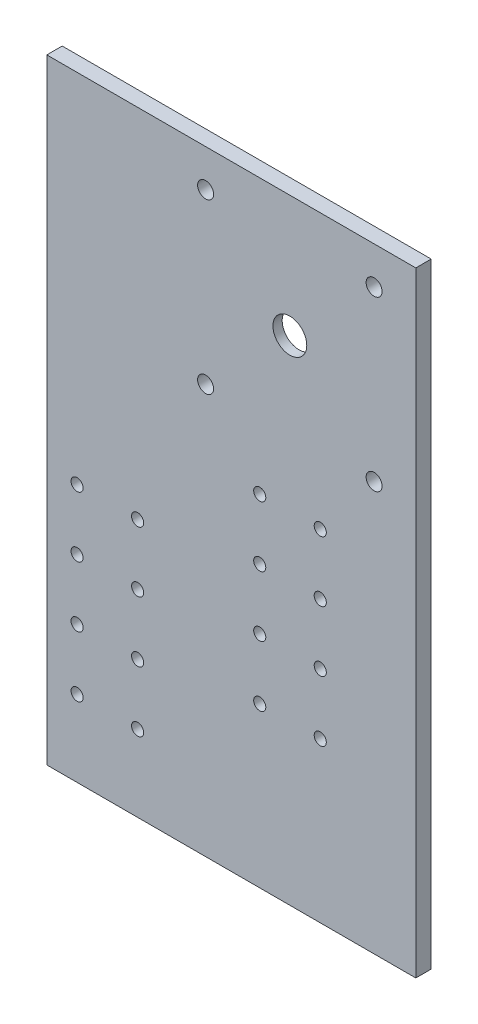
SolidWorks part; units mm, degrees
material "6061 Alloy"
ref_plane "Front Plane" through (0, 0, 0) normal (0, 0, 1) x (1, 0, 0)
ref_plane "Top Plane" through (0, 0, 0) normal (0, 1, 0) x (1, 0, 0)
ref_plane "Right Plane" through (0, 0, 0) normal (1, 0, 0) x (0, 0, -1)
sketch "Sketch1" plane through (0, 0, 0) normal (0, 0, 1) x (1, 0, 0)
  line L1 (-76.2, 127) -> (76.2, 127)
  line L2 (-76.2, 127) -> (-76.2, -127)
  line L3 (-76.2, -127) -> (76.2, -127)
  line L4 (76.2, 127) -> (76.2, -127)
  line L5 (-76.2, 127) -> (76.2, -127) construction
  line L6 (-76.2, -127) -> (76.2, 127) construction
  point P0 (0, 0)
  dimension "D1" = 254
  dimension "D2" = 152.4
extrude "Boss-Extrude1" add sketch "Sketch1" along normal blind 6.35
sketch "Sketch2" plane through (0, 0, 6.35) normal (0, 0, 1) x (1, 0, 0)
  circle A0 centre (58.979, 111.5609) radius 3.302 construction
  circle A1 centre (58.979, 111.5609) radius 3.302
  circle A2 centre (-10.617, 111.5609) radius 3.302 construction
  circle A3 centre (-10.617, 111.5609) radius 3.302
  circle A4 centre (58.98, 41.9649) radius 3.302 construction
  circle A5 centre (58.98, 41.9649) radius 3.302
  circle A6 centre (-10.618, 41.9639) radius 3.302 construction
  circle A7 centre (-10.618, 41.9639) radius 3.302
extrude "Cut-Extrude1" cut sketch "Sketch2" against normal up to next
sketch "Sketch3" plane through (0, 0, 0) normal (0, 0, -1) x (-1, 0, 0)
  circle A0 centre (63.7, -20.45) radius 2.5 construction
  circle A1 centre (63.7, -20.45) radius 2.5
  circle A2 centre (38.7, -20.45) radius 2.5 construction
  circle A3 centre (38.7, -45.45) radius 2.5 construction
  circle A4 centre (63.7, -45.45) radius 2.5 construction
  circle A5 centre (63.7, -70.45) radius 2.5 construction
  circle A6 centre (38.7, -70.45) radius 2.5 construction
  circle A7 centre (38.7, -95.45) radius 2.5 construction
  circle A8 centre (63.7, -95.45) radius 2.5 construction
  circle A9 centre (38.7, -20.45) radius 2.5
  circle A10 centre (38.7, -45.45) radius 2.5
  circle A11 centre (63.7, -45.45) radius 2.5
  circle A12 centre (63.7, -70.45) radius 2.5
  circle A13 centre (38.7, -70.45) radius 2.5
  circle A14 centre (38.7, -95.45) radius 2.5
  circle A15 centre (63.7, -95.45) radius 2.5
  circle A16 centre (-11.738, -61.16) radius 2.5 construction
  circle A17 centre (-11.738, -36.16) radius 2.5 construction
  circle A18 centre (-36.738, -61.16) radius 2.5 construction
  circle A19 centre (-36.738, -36.16) radius 2.5 construction
  circle A20 centre (-11.738, -11.16) radius 2.5 construction
  circle A21 centre (-36.738, -11.16) radius 2.5 construction
  circle A22 centre (-36.738, 13.84) radius 2.5 construction
  circle A23 centre (-11.738, 13.84) radius 2.5 construction
  circle A24 centre (-11.738, -61.16) radius 2.5
  circle A25 centre (-11.738, -36.16) radius 2.5
  circle A26 centre (-36.738, -61.16) radius 2.5
  circle A27 centre (-36.738, -36.16) radius 2.5
  circle A28 centre (-11.738, -11.16) radius 2.5
  circle A29 centre (-36.738, -11.16) radius 2.5
  circle A30 centre (-36.738, 13.84) radius 2.5
  circle A31 centre (-11.738, 13.84) radius 2.5
extrude "Cut-Extrude2" cut sketch "Sketch3" against normal up to next
sketch "Sketch4" plane through (0, 0, 0) normal (0, 0, -1) x (-1, 0, 0)
  circle A0 centre (-24.1805, 76.7624) radius 36.5125 construction
  circle A1 centre (-24.1805, 76.7624) radius 36.5125
extrude "Cut-Extrude3" cut sketch "Sketch4" against normal blind 2.54
sketch "Sketch6" plane through (0, 0, 6.35) normal (0, 0, 1) x (1, 0, 0)
  circle A8 centre (24.1805, 76.7624) radius 6.985
extrude "Cut-Extrude4" cut sketch "Sketch6" against normal up to next
